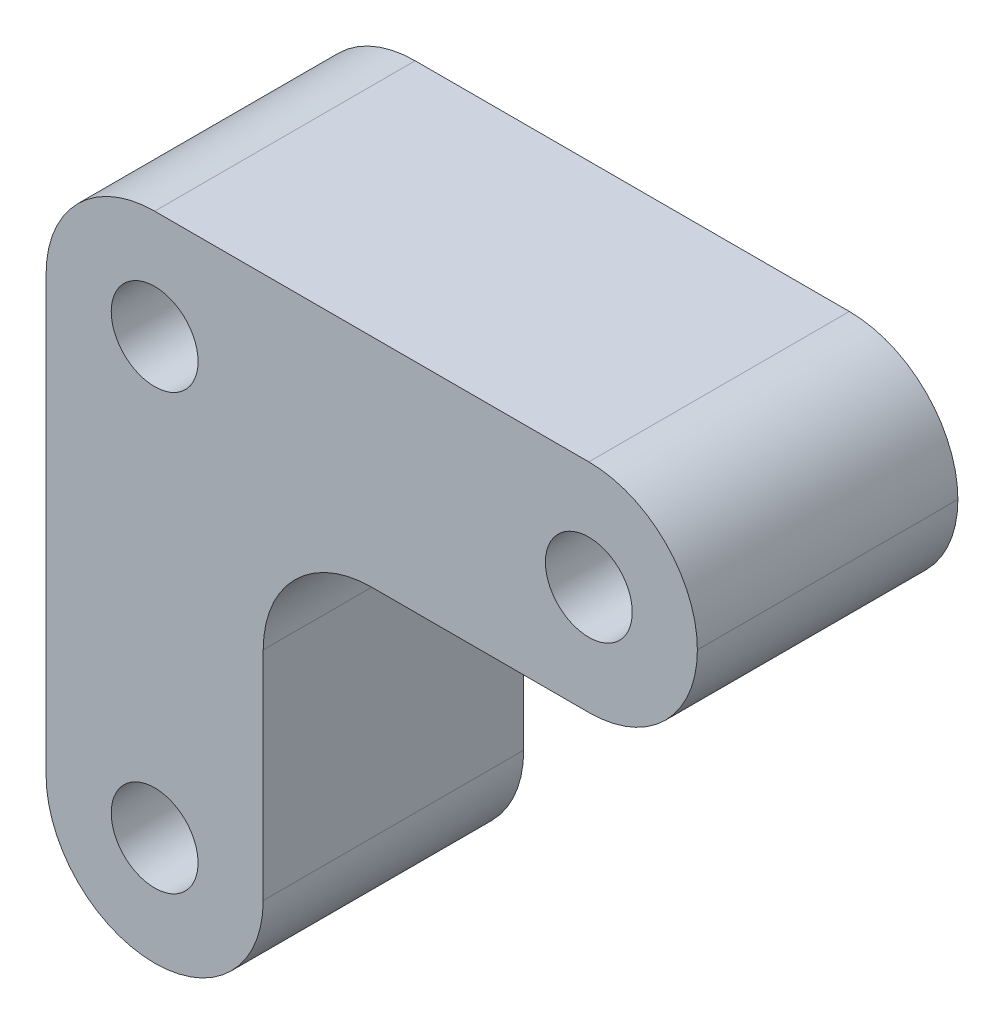
SolidWorks part; units mm, degrees
ref_plane "Front" through (0, 0, 0) normal (0, 0, 1) x (1, 0, 0)
ref_plane "Top" through (0, 0, 0) normal (0, 1, 0) x (1, 0, 0)
ref_plane "Right" through (0, 0, 0) normal (1, 0, 0) x (0, 0, -1)
sketch "Esquisse1" plane through (0, 0, 0) normal (0, 0, 1) x (1, 0, 0)
  line L1 (0, 0) -> (30, 0)
  line L2 (0, 0) -> (0, 30)
  line L3 (0, 30) -> (30, 30)
  line L4 (30, 0) -> (30, 30)
  dimension "D1" = 30
  dimension "D2" = 30
extrude "Boss.-Extru.1" add sketch "Esquisse1" along normal blind 12
sketch "Esquisse2" plane through (0, 0, 12) normal (0, 0, 1) x (1, 0, 0)
  line L0 (15, 0) -> (15, 30) construction
  line L1 (0, 0) -> (30, 0) construction
  line L2 (30, 30) -> (0, 30) construction
  line L3 (15, 15) -> (0, 15) construction
  line L4 (0, 30) -> (0, 0) construction
  circle A0 centre (5, 25) radius 2
  circle A1 centre (25, 25) radius 2
  circle A2 centre (25, 5) radius 2
  circle A3 centre (5, 5) radius 2
  dimension "D1" = 20
  dimension "D2" = 20
  dimension "D3" = 4
extrude "Enlèv. mat.-Extru.1" cut sketch "Esquisse2" against normal through all both and the other way through all
sketch "Esquisse3" plane through (0, 0, 12) normal (0, 0, 1) x (1, 0, 0)
  line L0 (30, 30) -> (0, 30) construction
  line L1 (30, 0) -> (10, 0)
  line L2 (30, 0) -> (30, 20)
  line L3 (30, 20) -> (10, 20)
  line L4 (10, 0) -> (10, 20)
  line L5 (0, 30) -> (0, 0) construction
  dimension "D1" = 10
  dimension "D2" = 10
extrude "Enlèv. mat.-Extru.2" cut sketch "Esquisse3" against normal through all both and the other way through all
fillet "Congé1" radius 5 6 edges at (10, 20, 6) (0, 30, 6) (0, 0, 6) (10, 0, 6) (30, 30, 6) (30, 20, 6)
